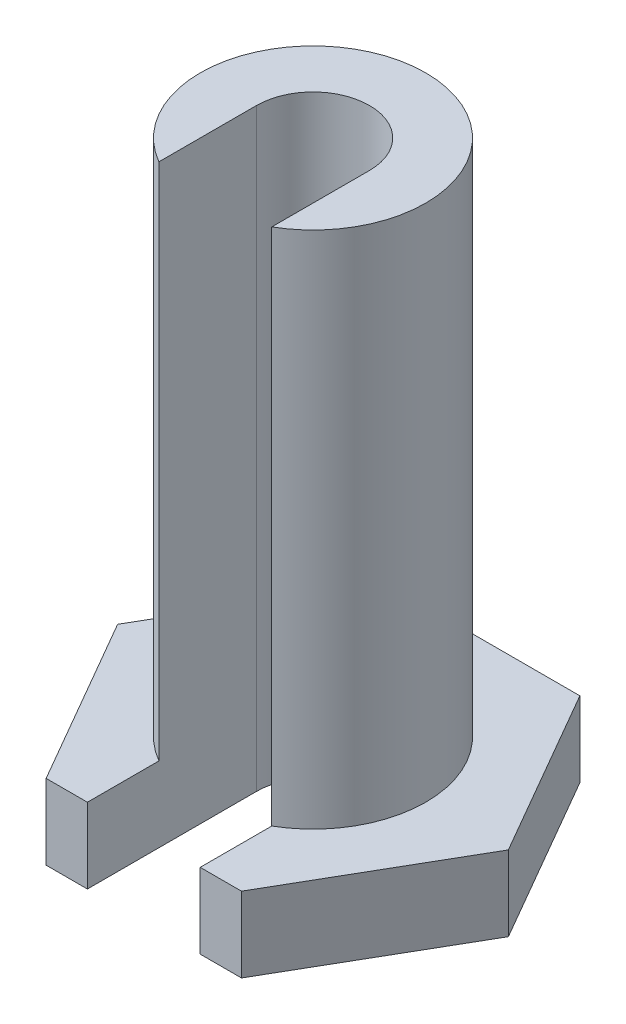
SolidWorks part; units mm, degrees
ref_plane "Front Plane" through (0, 0, 0) normal (0, 0, 1) x (1, 0, 0)
ref_plane "Top Plane" through (0, 0, 0) normal (0, 1, 0) x (1, 0, 0)
ref_plane "Right Plane" through (0, 0, 0) normal (1, 0, 0) x (0, 0, -1)
sketch "Sketch1" plane through (0, 0, 0) normal (0, 1, 0) x (1, 0, 0)
  circle A0 centre (0, 0) radius 3
  dimension "D1" = 6
extrude "Boss-Extrude1" add sketch "Sketch1" along normal blind 15.8
sketch "Sketch3" plane through (0, 0, 0) normal (0, -1, 0) x (-1, 0, 0)
  line L1 (5.1962, 0) -> (2.5981, 4.5)
  line L2 (2.5981, 4.5) -> (-2.5981, 4.5)
  line L3 (-2.5981, 4.5) -> (-5.1962, 0)
  line L4 (-5.1962, 0) -> (-2.5981, -4.5)
  line L5 (-2.5981, -4.5) -> (2.5981, -4.5)
  line L6 (2.5981, -4.5) -> (5.1962, 0)
  circle A0 centre (0, 0) radius 4.5 construction
extrude "Boss-Extrude2" add sketch "Sketch3" against normal blind 2
sketch "Sketch4" plane through (0, 15.8, 0) normal (0, 1, 0) x (1, 0, 0)
  line L0 (-1.5, 0) -> (-1.5, -4.5)
  line L1 (2.5981, -4.5) -> (-2.5981, -4.5) construction
  line L2 (-1.5, -4.5) -> (1.5, -4.5)
  line L3 (1.5, -4.5) -> (1.5, 0)
  arc A0 (1.5, 0) -> (-1.5, 0) centre (0, 0) ccw
  dimension "D1" = 3
extrude "Cut-Extrude1" cut sketch "Sketch4" against normal through all both and the other way through all
